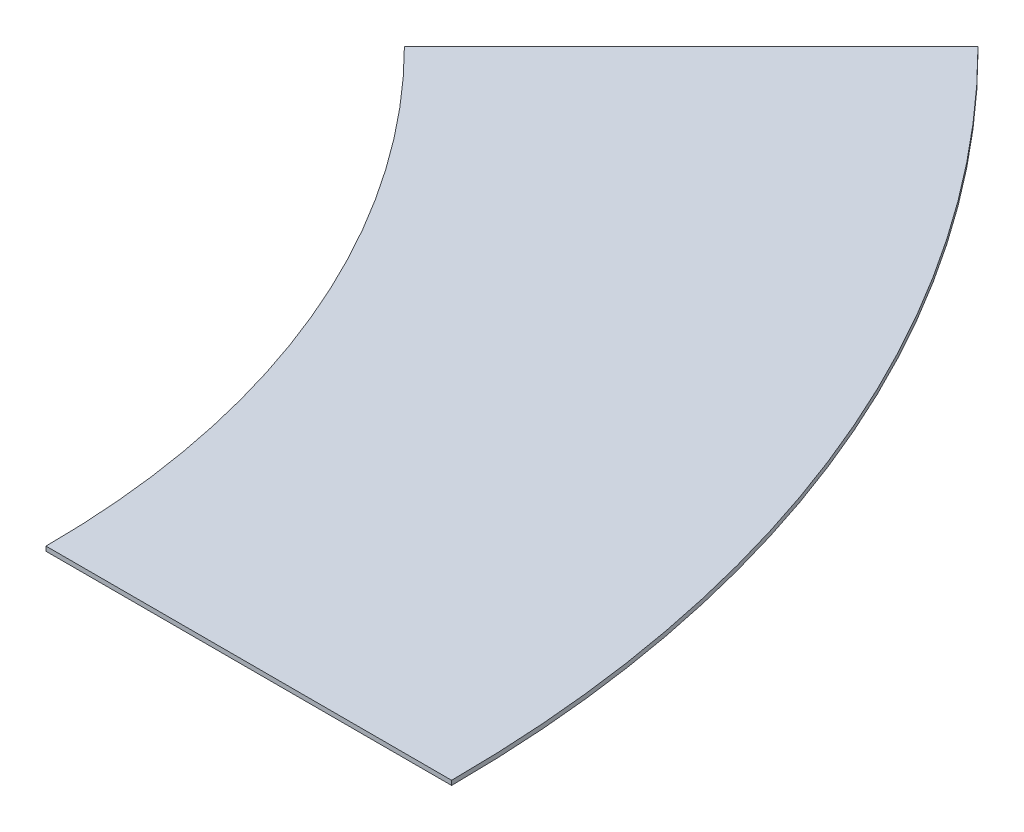
SolidWorks part; units mm, degrees
material "PE High Density"
ref_plane "Front Plane" through (0, 0, 0) normal (0, 0, 1) x (1, 0, 0)
ref_plane "Top Plane" through (0, 0, 0) normal (0, 1, 0) x (1, 0, 0)
ref_plane "Right Plane" through (0, 0, 0) normal (1, 0, 0) x (0, 0, -1)
sketch "Sketch2" plane through (0, 0, 0) normal (0, 0, 1) x (1, 0, 0)
  line L0 (0, 0) -> (0, 22.7316) construction
  line L1 (0, 0) -> (960, 0)
  line L2 (960, 2.5) -> (960, -2.5)
  line L3 (960, 2.5) -> (1410, 2.5)
  line L4 (1410, 2.5) -> (1410, -2.5)
  line L5 (1410, -2.5) -> (960, -2.5)
  point P7 (960, 0)
revolve "Revolve1" add sketch "Sketch2" angle 45 about L0
